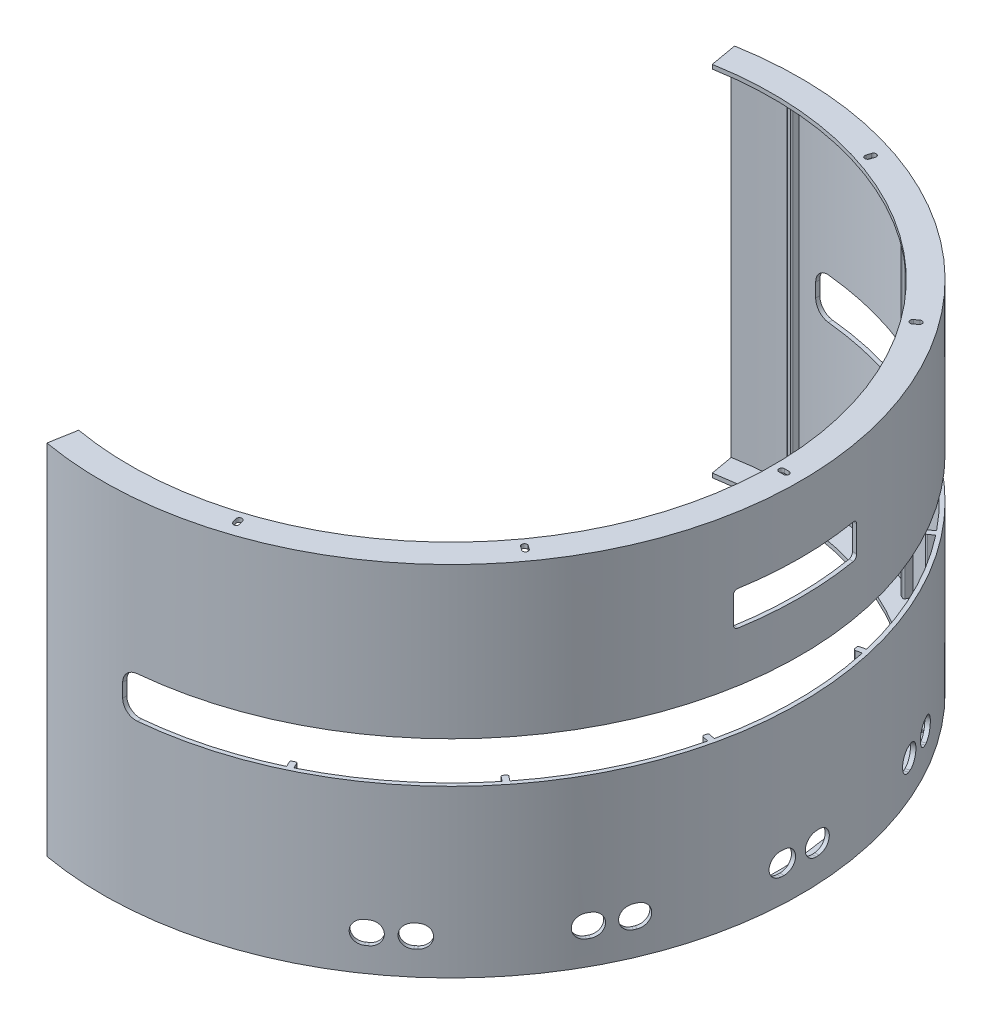
SolidWorks part; units mm, degrees
ref_plane "Front Plane" through (0, 0, 0) normal (0, 0, 1) x (1, 0, 0)
ref_plane "Top Plane" through (0, 0, 0) normal (0, 1, 0) x (1, 0, 0)
ref_plane "Right Plane" through (0, 0, 0) normal (1, 0, 0) x (0, 0, -1)
sketch "Sketch3" plane through (0, 0, 0) normal (0, 1, 0) x (1, 0, 0)
  line L0 (0, -251.5) -> (0, 251.5)
  line L1 (-44.1935, 250.6336) -> (-43.6725, 247.6791)
  line L2 (-43.6725, -247.6791) -> (-44.1935, -250.6336)
  arc A0 (0, 251.5) -> (0, -251.5) centre (0, 0) cw
  arc A1 (0, 251.5) -> (-43.6725, 247.6791) centre (0, 0) ccw
  arc A2 (0, -251.5) -> (-43.6725, -247.6791) centre (0, 0) cw
  arc A3 (0, 254.5) -> (0, -254.5) centre (0, 0) cw
  arc A4 (0, 254.5) -> (-44.1935, 250.6336) centre (0, 0) ccw
  arc A5 (0, -254.5) -> (-44.1935, -250.6336) centre (0, 0) cw
  point P4 (0, 0)
  dimension "D1" = 503
  dimension "D2" = 3
  dimension "D3" = 3
  dimension "D4" = 3
extrude "Boss-Extrude1" add sketch "Sketch3" along normal blind 255 contours A5 A3 A4 L1 A1 A0 A2 L2 region at (252.0902, 0, 0)
sketch "Sketch6" plane through (0, 255, 0) normal (0, 1, 0) x (1, 0, 0)
  line L0 (0, -256) -> (0, 256)
  line L1 (-2, 253.0819) -> (-2, 247.0819)
  line L2 (-1, 246.0819) -> (1, 246.0819)
  line L3 (2, 247.0819) -> (2, 253.0819)
  line L4 (-2, 253.0819) -> (2, 253.0819)
  line L54 (108.0062, 228.8867) -> (105.4029, 223.4809)
  line L55 (105.87, 222.146) -> (107.6719, 221.2783)
  line L56 (109.0068, 221.7454) -> (111.6101, 227.1512)
  line L57 (108.0062, 228.8867) -> (111.6101, 227.1512)
  line L58 (196.6204, 159.3577) -> (191.9294, 155.6167)
  line L59 (191.7711, 154.2114) -> (193.0181, 152.6477)
  line L60 (194.4234, 152.4894) -> (199.1144, 156.2303)
  line L61 (196.6204, 159.3577) -> (199.1144, 156.2303)
  line L62 (246.2916, 58.2659) -> (240.442, 56.9308)
  line L63 (239.6896, 55.7333) -> (240.1347, 53.7835)
  line L64 (241.3321, 53.031) -> (247.1817, 54.3662)
  line L65 (246.2916, 58.2659) -> (247.1817, 54.3662)
  line L66 (247.1817, -54.3662) -> (241.3321, -53.031)
  line L67 (240.1347, -53.7835) -> (239.6896, -55.7333)
  line L68 (240.442, -56.9308) -> (246.2916, -58.2659)
  line L69 (247.1817, -54.3662) -> (246.2916, -58.2659)
  line L70 (199.1144, -156.2303) -> (194.4234, -152.4894)
  line L71 (193.0181, -152.6477) -> (191.7711, -154.2114)
  line L72 (191.9294, -155.6167) -> (196.6204, -159.3577)
  line L73 (199.1144, -156.2303) -> (196.6204, -159.3577)
  line L74 (111.6101, -227.1512) -> (109.0068, -221.7454)
  line L75 (107.6719, -221.2783) -> (105.87, -222.146)
  line L76 (105.4029, -223.4809) -> (108.0062, -228.8867)
  line L77 (111.6101, -227.1512) -> (108.0062, -228.8867)
  line L78 (2, -253.0819) -> (2, -247.0819)
  line L79 (1, -246.0819) -> (-1, -246.0819)
  line L80 (-2, -247.0819) -> (-2, -253.0819)
  line L81 (2, -253.0819) -> (-2, -253.0819)
  arc A2 (2, 247.0819) -> (1, 246.0819) centre (1, 247.0819) cw
  arc A3 (-2, 247.0819) -> (-1, 246.0819) centre (-1, 247.0819) ccw
  arc A26 (109.0068, 221.7454) -> (107.6719, 221.2783) centre (108.1058, 222.1792) cw
  arc A27 (105.4029, 223.4809) -> (105.87, 222.146) centre (106.3039, 223.047) ccw
  arc A28 (194.4234, 152.4894) -> (193.0181, 152.6477) centre (193.7999, 153.2712) cw
  arc A29 (191.9294, 155.6167) -> (191.7711, 154.2114) centre (192.5529, 154.8349) ccw
  arc A30 (241.3321, 53.031) -> (240.1347, 53.7835) centre (241.1096, 54.006) cw
  arc A31 (240.442, 56.9308) -> (239.6896, 55.7333) centre (240.6645, 55.9558) ccw
  arc A32 (240.442, -56.9308) -> (239.6896, -55.7333) centre (240.6645, -55.9558) cw
  arc A33 (241.3321, -53.031) -> (240.1347, -53.7835) centre (241.1096, -54.006) ccw
  arc A34 (191.9294, -155.6167) -> (191.7711, -154.2114) centre (192.5529, -154.8349) cw
  arc A35 (194.4234, -152.4894) -> (193.0181, -152.6477) centre (193.7999, -153.2712) ccw
  arc A36 (105.4029, -223.4809) -> (105.87, -222.146) centre (106.3039, -223.047) cw
  arc A37 (109.0068, -221.7454) -> (107.6719, -221.2783) centre (108.1058, -222.1792) ccw
  arc A38 (-2, -247.0819) -> (-1, -246.0819) centre (-1, -247.0819) cw
  arc A39 (2, -247.0819) -> (1, -246.0819) centre (1, -247.0819) ccw
  point P9 (0, 0)
  point P19 (2, 246.0819)
  point P22 (-2, 246.0819)
  point P23 (0, 246.0819)
  point P59 (0, 0)
  point P68 (0, 0)
  point P76 (0, 0)
  dimension "D3" = 1
  dimension "D1" = 7
  dimension "D2" = 4
  dimension "D4" = 0
  dimension "D5" = 7
  dimension "D6" = 256
  dimension "D7" = 8
extrude "Boss-Extrude2" add sketch "Sketch6" against normal blind 255 separate body contours L3 L4 L1 A3 L2 A2 | L56 L57 L54 A27 L55 A26 | L60 L61 L58 A29 L59 A28 | L64 L65 L62 A31 L63 A30 | L68 L69 L66 A33 L67 A32 | L72 L73 L70 A35 L71 A34 | L76 L77 L74 A37 L75 A36 | L78 A39 L79 A38 L80 L81
combine bodies "Combine2" operation type add bodies to combine 109 101 115 116 117 118 119 120 121
sketch "Sketch4" plane through (0, 0, 0) normal (0, 0, 1) x (1, 0, 0)
  line L0 (254.5, 0) -> (254.5, 255) construction
  line L1 (494.5, 118) -> (14.5, 118)
  line L2 (494.5, 118) -> (494.5, 148)
  line L3 (494.5, 148) -> (14.5, 148)
  line L4 (14.5, 118) -> (14.5, 148)
  line L5 (494.5, 118) -> (14.5, 148) construction
  line L6 (494.5, 148) -> (14.5, 118) construction
  line L7 (-44.1935, 0) -> (254.5, 0) construction
  point P0 (254.5, 133)
  dimension "D1" = 30
  dimension "D2" = 118
  dimension "D3" = 480
extrude "Cut-Extrude2" cut sketch "Sketch4" against normal mid plane 953
fillet "Fillet2" radius 10 4 edges at (14.5, 148, -252.5841) (14.5, 118, -252.5841) (14.5, 118, 252.5841) (14.5, 148, 252.5841)
sketch "Sketch7" plane through (0, 255, 0) normal (0, 1, 0) x (1, 0, 0)
  line L0 (-44.1935, 250.6336) -> (-40.7205, 230.9374)
  line L1 (-44.1935, -250.6336) -> (-40.7205, -230.9374)
  arc A0 (-40.7205, 230.9374) -> (-40.7205, -230.9374) centre (0, 0) cw
  arc A2 (-44.1935, 250.6336) -> (-44.1935, -250.6336) centre (0, 0) cw
  arc A3 (-44.1935, -250.6336) -> (-44.1935, 250.6336) centre (0, 0) ccw construction
extrude "Boss-Extrude3" add sketch "Sketch7" along normal blind 3 contours A2 L0 A0 L1 region at (248.5983, 255, 0)
sketch "Sketch8" plane through (0, 255, 0) normal (0, -1, 0) x (1, 0, 0)
  line L0 (240.8, 0) -> (244.2, 0) construction
  line L1 (240.8, 2) -> (244.2, 2)
  line L2 (240.8, -2) -> (244.2, -2)
  line L3 (194.8113, -141.5387) -> (197.562, -143.5372) construction
  line L12 (195.9869, -139.9207) -> (198.7375, -141.9191)
  line L21 (193.6357, -143.1567) -> (196.3864, -145.1552)
  line L24 (74.4113, -229.0144) -> (75.462, -232.248) construction
  line L27 (76.3134, -228.3964) -> (77.3641, -231.63)
  line L28 (72.5092, -229.6324) -> (73.5598, -232.866)
  line L29 (-74.4113, -229.0144) -> (-75.462, -232.248) construction
  line L30 (-72.5092, -229.6324) -> (-73.5598, -232.866)
  line L31 (-76.3134, -228.3964) -> (-77.3641, -231.63)
  line L32 (-194.8113, -141.5387) -> (-197.562, -143.5372) construction
  line L33 (-193.6357, -143.1567) -> (-196.3864, -145.1552)
  line L34 (-195.9869, -139.9207) -> (-198.7375, -141.9191)
  line L35 (-240.8, 0) -> (-244.2, 0) construction
  line L36 (-240.8, -2) -> (-244.2, -2)
  line L37 (-240.8, 2) -> (-244.2, 2)
  line L38 (-194.8113, 141.5387) -> (-197.562, 143.5372) construction
  line L39 (-195.9869, 139.9207) -> (-198.7375, 141.9191)
  line L40 (-193.6357, 143.1567) -> (-196.3864, 145.1552)
  line L41 (-74.4113, 229.0144) -> (-75.462, 232.248) construction
  line L42 (-76.3134, 228.3964) -> (-77.3641, 231.63)
  line L43 (-72.5092, 229.6324) -> (-73.5598, 232.866)
  line L44 (74.4113, 229.0144) -> (75.462, 232.248) construction
  line L45 (72.5092, 229.6324) -> (73.5598, 232.866)
  line L46 (76.3134, 228.3964) -> (77.3641, 231.63)
  line L47 (194.8113, 141.5387) -> (197.562, 143.5372) construction
  line L48 (193.6357, 143.1567) -> (196.3864, 145.1552)
  line L49 (195.9869, 139.9207) -> (198.7375, 141.9191)
  circle A1 centre (242.5, 0) radius 1.7 construction
  arc A2 (240.8, 2) -> (240.8, -2) centre (240.8, 0) ccw
  arc A3 (244.2, -2) -> (244.2, 2) centre (244.2, 0) ccw
  arc A24 (195.9869, -139.9207) -> (193.6357, -143.1567) centre (194.8113, -141.5387) ccw
  arc A25 (196.3864, -145.1552) -> (198.7375, -141.9191) centre (197.562, -143.5372) ccw
  arc A26 (76.3134, -228.3964) -> (72.5092, -229.6324) centre (74.4113, -229.0144) ccw
  arc A27 (73.5598, -232.866) -> (77.3641, -231.63) centre (75.462, -232.248) ccw
  arc A28 (-72.5092, -229.6324) -> (-76.3134, -228.3964) centre (-74.4113, -229.0144) ccw
  arc A29 (-77.3641, -231.63) -> (-73.5598, -232.866) centre (-75.462, -232.248) ccw
  arc A30 (-193.6357, -143.1567) -> (-195.9869, -139.9207) centre (-194.8113, -141.5387) ccw
  arc A31 (-198.7375, -141.9191) -> (-196.3864, -145.1552) centre (-197.562, -143.5372) ccw
  arc A32 (-240.8, -2) -> (-240.8, 2) centre (-240.8, 0) ccw
  arc A33 (-244.2, 2) -> (-244.2, -2) centre (-244.2, 0) ccw
  arc A34 (-195.9869, 139.9207) -> (-193.6357, 143.1567) centre (-194.8113, 141.5387) ccw
  arc A35 (-196.3864, 145.1552) -> (-198.7375, 141.9191) centre (-197.562, 143.5372) ccw
  arc A36 (-76.3134, 228.3964) -> (-72.5092, 229.6324) centre (-74.4113, 229.0144) ccw
  arc A37 (-73.5598, 232.866) -> (-77.3641, 231.63) centre (-75.462, 232.248) ccw
  arc A38 (72.5092, 229.6324) -> (76.3134, 228.3964) centre (74.4113, 229.0144) ccw
  arc A39 (77.3641, 231.63) -> (73.5598, 232.866) centre (75.462, 232.248) ccw
  arc A40 (193.6357, 143.1567) -> (195.9869, 139.9207) centre (194.8113, 141.5387) ccw
  arc A41 (198.7375, 141.9191) -> (196.3864, 145.1552) centre (197.562, 143.5372) ccw
  point P6 (242.5, 0)
  point P16 (196.1866, -142.5379)
  point P23 (74.9366, -230.6312)
  point P28 (0, 0)
  point P31 (-74.9366, -230.6312)
  point P35 (0, 0)
  point P39 (-196.1866, -142.5379)
  point P44 (0, 0)
  point P47 (-242.5, 0)
  point P54 (-196.1866, 142.5379)
  point P57 (0, 0)
  point P62 (-74.9366, 230.6312)
  point P69 (74.9366, 230.6312)
  point P76 (196.1866, 142.5379)
  point P81 (0, 0)
  dimension "D1" = 2
extrude "Cut-Extrude3" cut sketch "Sketch8" against normal blind 5
pattern_linear "LPattern1" count 2 spacing 258 along (0, -1, 0) of "Boss-Extrude3"
pattern_linear "LPattern2" count 2 spacing 258 along (0, -1, 0) of "Cut-Extrude3"
sketch "Sketch9" plane through (0, 0, 0) normal (0, 0, 1) x (1, 0, 0)
  line L0 (254.5, 148) -> (254.5, 258) construction
  line L1 (268.0504, 184.5) -> (240.9496, 184.5)
  line L2 (268.0504, 184.5) -> (268.0504, 209.5)
  line L3 (268.0504, 209.5) -> (240.9496, 209.5)
  line L4 (240.9496, 184.5) -> (240.9496, 209.5)
  line L5 (268.0504, 184.5) -> (240.9496, 209.5) construction
  line L6 (268.0504, 209.5) -> (240.9496, 184.5) construction
  point P0 (254.5, 197)
  dimension "D1" = 25
  dimension "D2" = 200
extrude "Cut-Extrude4" cut sketch "Sketch9" against normal mid plane 90
fillet "Fillet3" radius 3 4 edges at (248.9657, 209.5, 45) (248.9657, 184.5, 45) (248.9657, 184.5, -45) (248.9657, 209.5, -45)
sketch "Sketch10" plane through (0, 0, 0) normal (1, 0, 0) x (0, 0, -1)
  line L0 (13.75, 23) -> (11.75, 23) construction
  line L1 (13.75, 14.8) -> (11.75, 14.8)
  line L2 (13.75, 31.2) -> (11.75, 31.2)
  line L3 (0, 143.55) -> (0, -143.55) construction
  line L4 (-13.75, 23) -> (-11.75, 23) construction
  line L5 (-13.75, 14.8) -> (-11.75, 14.8)
  line L6 (-13.75, 31.2) -> (-11.75, 31.2)
  arc A0 (13.75, 14.8) -> (13.75, 31.2) centre (13.75, 23) ccw
  arc A1 (11.75, 31.2) -> (11.75, 14.8) centre (11.75, 23) ccw
  arc A2 (-13.75, 14.8) -> (-13.75, 31.2) centre (-13.75, 23) cw
  arc A3 (-11.75, 31.2) -> (-11.75, 14.8) centre (-11.75, 23) cw
  point P2 (12.75, 23)
  point P12 (-12.75, 23)
  dimension "D1" = 8.2
  dimension "D2" = 2
  dimension "D3" = 12.75
  dimension "D4" = 23
extrude "Cut-Extrude5" cut sketch "Sketch10" along normal blind 600
pattern_circular "CirPattern1" count 3 every 26 about axis through (0, 255, 0) along (0, -1, 0) of "Cut-Extrude5" reverse direction yes
pattern_circular "CirPattern2" count 3 every 26 about axis through (0, 255, 0) along (0, -1, 0) of "Cut-Extrude5"
